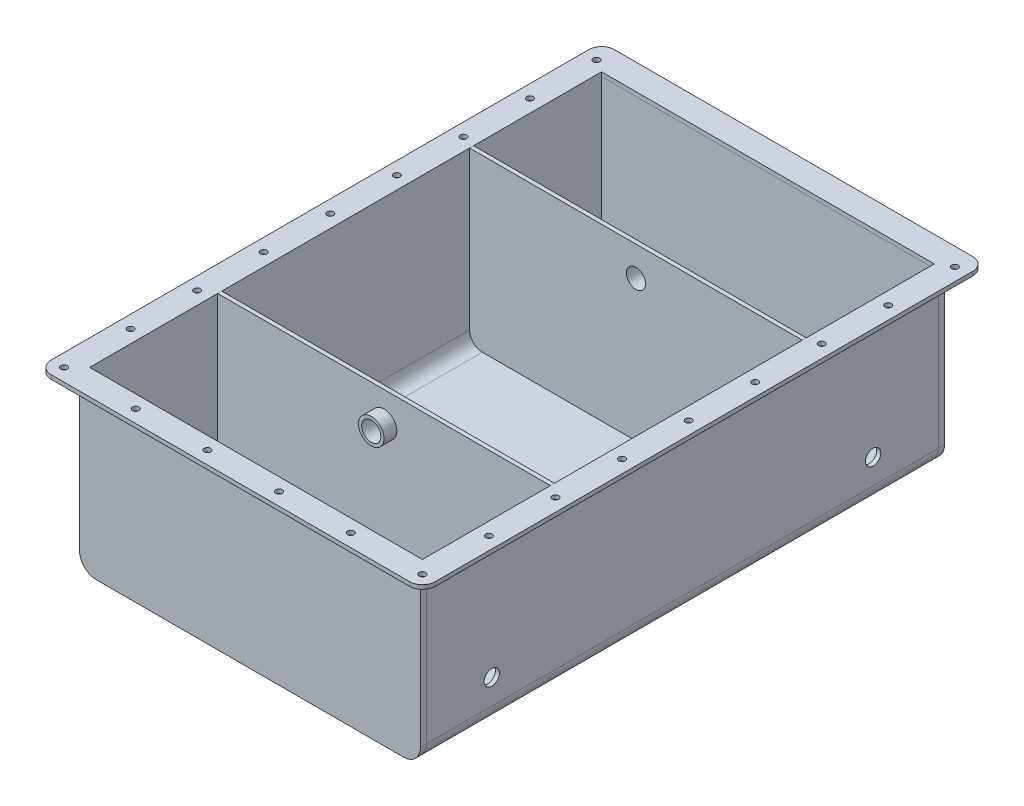
SolidWorks part; units mm, degrees
material "5052-H32"
ref_plane "Front Plane" through (0, 0, 0) normal (0, 0, 1) x (1, 0, 0)
ref_plane "Top Plane" through (0, 0, 0) normal (0, 1, 0) x (1, 0, 0)
ref_plane "Right Plane" through (0, 0, 0) normal (1, 0, 0) x (0, 0, -1)
sketch "Sketch2" plane through (0, 0, 0) normal (0, 0, 1) x (1, 0, 0)
  line L0 (-130, 0) -> (130, 0)
  line L1 (-130, 0) -> (-130, 130)
  line L2 (130, 0) -> (130, 130)
  line L3 (-133.175, -3.175) -> (-133.175, 130)
  line L4 (-133.175, -3.175) -> (133.175, -3.175)
  line L5 (133.175, -3.175) -> (133.175, 130)
  line L6 (-133.175, 130) -> (-130, 130)
  line L7 (130, 130) -> (133.175, 130)
  point P4 (0, 0)
  dimension "D1" = 260
  dimension "D3" = 130
  dimension "D4" = 130
  dimension "D2" = 3.175
  dimension "D5" = 3.175
  dimension "D6" = 3.175
extrude "Interior Dim" add sketch "Sketch2" against normal blind 400
fillet "Fillet2" radius 10 2 edges at (-130, 0, -200) (130, 0, -200)
fillet "Fillet3" radius 13.175 2 edges at (-133.175, -3.175, -200) (133.175, -3.175, -200)
ref_plane "Plane1" through (0, 0, 0) normal (0, 0, 1) x (1, 0, 0)
sketch "Sketch4" plane through (0, 0, 0) normal (0, 0, 1) x (1, 0, 0)
  line L0 (-130, 130) -> (130, 130)
  line L9 (-120, -3.175) -> (120, -3.175)
  line L10 (133.175, 10) -> (133.175, 130)
  line L11 (133.175, 130) -> (130, 130)
  line L12 (130, 130) -> (130, 10)
  line L13 (120, 0) -> (-120, 0)
  line L14 (-130, 10) -> (-130, 130)
  line L15 (-130, 130) -> (-133.175, 130)
  line L16 (-133.175, 130) -> (-133.175, 10)
  line L17 (-120, -3.175) -> (120, -3.175)
  line L18 (133.175, 10) -> (133.175, 130)
  line L19 (133.175, 130) -> (130, 130)
  line L23 (-130, 130) -> (-133.175, 130)
  line L24 (-133.175, 130) -> (-133.175, 10)
  arc A4 (120, -3.175) -> (133.175, 10) centre (120, 10) ccw
  arc A5 (120, 0) -> (130, 10) centre (120, 10) ccw
  arc A6 (-130, 10) -> (-120, 0) centre (-120, 10) ccw
  arc A7 (120, -3.175) -> (133.175, 10) centre (120, 10) ccw
  arc A9 (-133.175, 10) -> (-120, -3.175) centre (-120, 10) ccw
  arc A10 (-133.175, 10) -> (-120, -3.175) centre (-120, 10) ccw
  dimension "D1" = 0
extrude "Endcap1" add sketch "Sketch4" along normal blind 4.7625 separate body
ref_plane "Plane2" through (0, 0, -400) normal (0, 0, -1) x (-1, 0, 0)
sketch "Sketch5" plane through (0, 0, -400) normal (0, 0, -1) x (-1, 0, 0)
  line L8 (133.175, 130) -> (-133.175, 130)
  line L16 (-133.175, 130) -> (-133.175, 10)
  line L17 (-120, -3.175) -> (120, -3.175)
  line L18 (133.175, 10) -> (133.175, 130)
  line L19 (133.175, 130) -> (130, 130)
  line L20 (130, 130) -> (130, 10)
  line L21 (120, 0) -> (-120, 0)
  line L22 (-130, 10) -> (-130, 130)
  line L23 (-130, 130) -> (-133.175, 130)
  line L24 (-133.175, 130) -> (-133.175, 10)
  line L25 (-120, -3.175) -> (120, -3.175)
  line L26 (133.175, 10) -> (133.175, 130)
  arc A6 (-133.175, 10) -> (-120, -3.175) centre (-120, 10) ccw
  arc A7 (-133.175, 10) -> (-120, -3.175) centre (-120, 10) ccw
  arc A8 (120, 0) -> (130, 10) centre (120, 10) ccw
  arc A9 (-130, 10) -> (-120, 0) centre (-120, 10) ccw
  arc A12 (120, -3.175) -> (133.175, 10) centre (120, 10) ccw
  arc A13 (120, -3.175) -> (133.175, 10) centre (120, 10) ccw
  dimension "D1" = 0
ref_plane "Compartment1" through (0, 0, -100) normal (0, 0, -1) x (-1, 0, 0)
sketch "Sketch7" plane through (0, 0, -100) normal (0, 0, -1) x (-1, 0, 0)
  line L1 (130, 130) -> (-130, 130)
  line L10 (-120, -3.175) -> (120, -3.175)
  line L11 (-133.175, 130) -> (-133.175, 10)
  line L12 (-130, 130) -> (-133.175, 130)
  line L13 (-130, 10) -> (-130, 130)
  line L14 (120, 0) -> (-120, 0)
  line L15 (130, 130) -> (130, 10)
  line L16 (133.175, 130) -> (130, 130)
  line L17 (133.175, 10) -> (133.175, 130)
  line L21 (-130, 10) -> (-130, 130)
  line L22 (120, 0) -> (-120, 0)
  line L23 (130, 130) -> (130, 10)
  arc A5 (-130, 10) -> (-120, 0) centre (-120, 10) ccw
  arc A6 (120, 0) -> (130, 10) centre (120, 10) ccw
  arc A7 (-133.175, 10) -> (-120, -3.175) centre (-120, 10) ccw
  arc A8 (120, -3.175) -> (133.175, 10) centre (120, 10) ccw
  arc A9 (-130, 10) -> (-120, 0) centre (-120, 10) ccw
  arc A10 (120, 0) -> (130, 10) centre (120, 10) ccw
  dimension "D1" = 0
extrude "Compartment1_Boss" add sketch "Sketch7" along normal blind 3.175 separate body contours L22 A10 L23 L1 L21 A9 region at (0, 65.0798, -100)
ref_plane "Plane5" through (0, 130, 0) normal (0, 1, 0) x (1, 0, 0)
sketch "Sketch9" plane through (0, 130, 0) normal (0, 1, 0) x (1, 0, 0)
  line L0 (73.2463, 400) -> (-73.2463, 400) construction
  line L1 (-130, 400) -> (130, 400)
  line L2 (-130, 400) -> (-130, 0)
  line L3 (-130, 0) -> (130, 0)
  line L4 (130, 400) -> (130, 0)
  line L5 (-130, 0) -> (-130, 400) construction
  line L6 (-73.2463, 0) -> (73.2463, 0) construction
  line L7 (130, 400) -> (130, 0) construction
  line L8 (-150, 420) -> (-150, -20)
  line L9 (-150, -20) -> (150, -20)
  line L10 (150, 420) -> (150, -20)
  line L11 (-150, 420) -> (150, 420)
  circle A0 centre (-140, -10) radius 2.5
  circle A2 centre (-140, 42) radius 2.5
  circle A3 centre (-140, 94) radius 2.5
  circle A4 centre (-140, 146) radius 2.5
  circle A5 centre (-140, 198) radius 2.5
  circle A6 centre (-140, 250) radius 2.5
  circle A7 centre (-140, 302) radius 2.5
  circle A8 centre (-140, 354) radius 2.5
  circle A9 centre (-140, 406) radius 2.5
  circle A10 centre (-140, 458) radius 2.5
  circle A16 centre (-140, 510) radius 2.5
  circle A17 centre (-84, 510) radius 2.5
  circle A18 centre (-28, 510) radius 2.5
  circle A19 centre (28, 510) radius 2.5
  circle A20 centre (84, 510) radius 2.5
  circle A21 centre (140, 510) radius 2.5
  circle A22 centre (140, 458) radius 2.5
  circle A23 centre (140, 406) radius 2.5
  circle A24 centre (140, 354) radius 2.5
  circle A25 centre (140, 302) radius 2.5
  circle A26 centre (140, 250) radius 2.5
  circle A27 centre (140, 198) radius 2.5
  circle A28 centre (140, 146) radius 2.5
  circle A29 centre (140, 94) radius 2.5
  circle A30 centre (140, 42) radius 2.5
  circle A31 centre (140, -10) radius 2.5
  circle A37 centre (84, -10) radius 2.5
  circle A38 centre (28, -10) radius 2.5
  circle A39 centre (-28, -10) radius 2.5
  circle A40 centre (-84, -10) radius 2.5
  dimension "D4" = 5
  dimension "D7" = 5
  dimension "D2" = 10
  dimension "D3" = 10
  dimension "D5" = 6
  dimension "D6" = 11
  dimension "D8" = 11
  dimension "D1" = 20
extrude "Lid_Flange" add sketch "Sketch9" along normal blind 3.175 separate body contours L11 L8 L9 L10 A31 A21 A20 A19 A18 A17 A16 A10 A9 A8 A7 A6 A5 A4 A3 A2 A0 L1 L4 region at (0, 130, -414.6746)
fillet "Fillet4" radius 10 4 edges at (-150, 131.5875, -420) (150, 131.5875, -420) (150, 131.5875, 20) (-150, 131.5875, 20)
extrude "Endcap2" add sketch "Sketch5" along normal blind 4.7625 separate body
ref_plane "Compartment2" through (0, 0, -300) normal (0, 0, 1) x (1, 0, 0)
sketch "Sketch13" plane through (0, 0, -300) normal (0, 0, 1) x (1, 0, 0)
  line L0 (130, 130) -> (-130, 130)
  line L1 (133.175, 130) -> (130, 130) construction
  line L2 (130, 130) -> (130, 10) construction
  line L3 (-140, 130) -> (140, 130) construction
  line L4 (-130, 10) -> (-130, 130) construction
  line L5 (130, 130) -> (130, 10)
  line L6 (-130, 130) -> (-130, 10)
  line L7 (120, 0) -> (-120, 0)
  arc A0 (120, 0) -> (130, 10) centre (120, 10) ccw construction
  arc A1 (-130, 10) -> (-120, 0) centre (-120, 10) ccw construction
  arc A2 (-130, 10) -> (-120, 0) centre (-120, 10) ccw
  arc A3 (130, 10) -> (120, 0) centre (120, 10) cw
  dimension "D1" = 130
extrude "Compartment2_Boss" add sketch "Sketch13" along normal blind 3.175
sketch "Sketch16" plane through (-133.175, 0, 0) normal (-1, 0, 0) x (0, 0, 1)
  line L0 (-400, 0) -> (-300, 0) construction
  line L1 (-400, 130) -> (-400, 10) construction
  line L2 (0, 130) -> (0, 10) construction
  line L3 (-51, 29.5) -> (-349, 29.5) construction
  circle A0 centre (-349, 29.5) radius 6
  circle A1 centre (-51, 29.5) radius 6
  dimension "D1" = 12
  dimension "D4" = 12
  dimension "D2" = 29.5
  dimension "D3" = 51
  dimension "D5" = 51
extrude "Bearing_holes" cut sketch "Sketch16" against normal through all
sketch "Sketch17" plane through (0, 0, -300) normal (0, 0, -1) x (-1, 0, 0)
  line L0 (142.7388, 130) -> (-142.7388, 130) construction
  line L1 (130, 130) -> (130, 10) construction
  circle A0 centre (0, 110) radius 7.5
  circle A1 centre (0, 110) radius 10
  dimension "D3" = 130
  dimension "D1" = 15
  dimension "D4" = 20
  dimension "D2" = 20
extrude "Wire_Passthrough" cut sketch "Sketch17" against normal up to surface (200 mm away) contours A0 region at (0, 110, -300) up to face at (0, 45.9763, -100)
sketch "Sketch18" plane through (0, 130, 0) normal (0, 1, 0) x (1, 0, 0)
  line L1 (-130, 300) -> (130, 300)
  line L2 (-130, 300) -> (-130, 296.825)
  line L3 (-130, 296.825) -> (130, 296.825)
  line L4 (130, 300) -> (130, 296.825)
  line L5 (-130, 103.175) -> (130, 103.175)
  line L6 (-130, 103.175) -> (-130, 100)
  line L7 (-130, 100) -> (130, 100)
  line L8 (130, 103.175) -> (130, 100)
extrude "Boss-Extrude1" add sketch "Sketch18" along normal blind 3.18
extrude "Wire_Tube_2" add sketch "Sketch17<3>" along normal blind 10
sketch "Sketch17<3>" plane through (0, 0, -300) normal (0, 0, -1) x (-1, 0, 0) same geometry as "Sketch17"
sketch "Sketch19" plane through (0, 0, -100) normal (0, 0, 1) x (1, 0, 0)
  circle A0 centre (0, 110) radius 10
  circle M1 centre (0, 110) radius 7.5
  dimension "D1" = 20
extrude "Wire_Tube_1" add sketch "Sketch19" along normal blind 10 contours A0 M1 region at (-9.7172, 110, -100)
equation "\"L\"= 400"
equation "\"W\"= 260"
equation "\"D1@Sketch2\"=\"W\""
equation "\"D1@Interior Dim\" = \"L\""
equation "\"H\"= 130"
equation "\"D3@Sketch2\"=\"H\""
equation "\"D4@Sketch2\"=\"H\""
equation "\"Compartment Width\"= 100"
equation "\"D1@Compartment2\"=\"Compartment Width\""
equation "\"D1@Compartment1\"=\"Compartment Width\""
equation "\"D1@Sketch13\"=\"H\""
equation "\"D3@Sketch17\"=\"W\"/2"
equation "\"T\"= 4.7625 * 2 / 3"
equation "\"D1@Lid_Flange\"=\"T\""
equation "\"D1@Fillet3\"=\"T\"+10"
equation "\"D1@Compartment1_Boss\"=\"T\""
equation "\"D1@Compartment2_Boss\"=\"T\""
